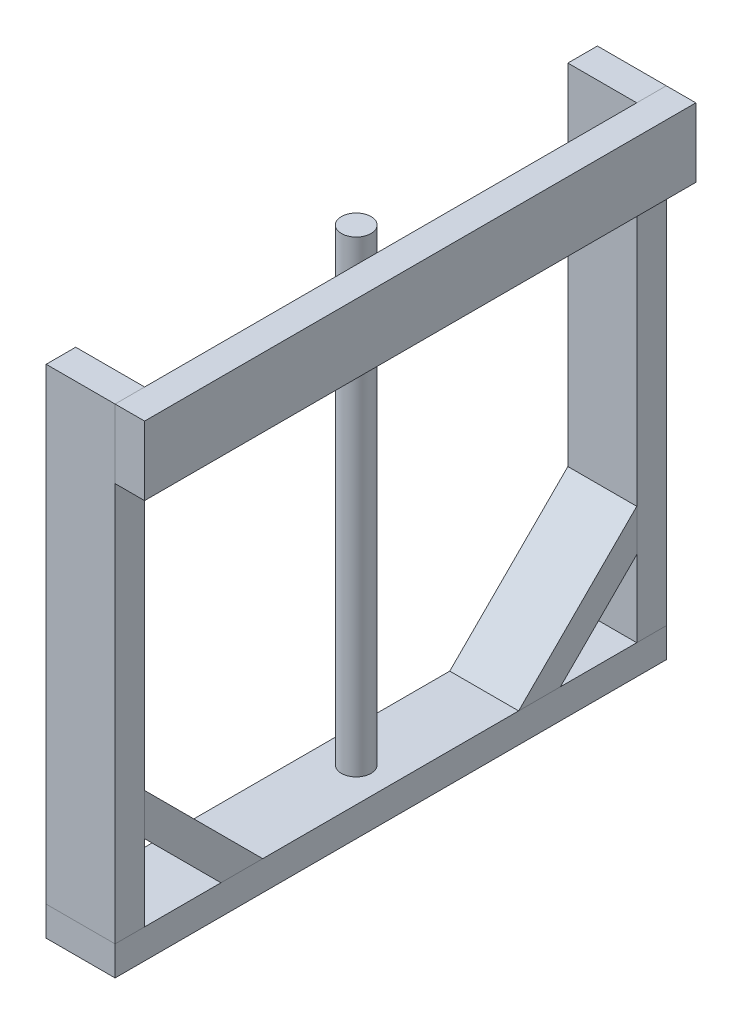
SolidWorks part; units mm, degrees
ref_plane "Front Plane" through (0, 0, 0) normal (0, 0, 1) x (1, 0, 0)
ref_plane "Top Plane" through (0, 0, 0) normal (0, 1, 0) x (1, 0, 0)
ref_plane "Right Plane" through (0, 0, 0) normal (1, 0, 0) x (0, 0, -1)
sketch "Sketch1" plane through (0, 0, 0) normal (1, 0, 0) x (0, 0, -1)
  line L1 (-355.6, 0) -> (355.6, 0)
  line L2 (-355.6, 0) -> (-355.6, -88.9)
  line L3 (-355.6, -88.9) -> (355.6, -88.9)
  line L4 (355.6, 0) -> (355.6, -88.9)
  dimension "D1" = 711.2
  dimension "D2" = 88.9
extrude "Top_Cross_Support" add sketch "Sketch1" along normal blind 38.1
sketch "Sketch2" plane through (0, 0, 0) normal (-1, 0, 0) x (0, 0, 1)
  line L1 (355.6, 0) -> (317.5, 0)
  line L2 (355.6, 0) -> (355.6, -603.25)
  line L3 (355.6, -603.25) -> (317.5, -603.25)
  line L4 (317.5, 0) -> (317.5, -603.25)
  dimension "D1" = 603.25
  dimension "D2" = 38.1
extrude "Leg" add sketch "Sketch2" along normal blind 88.9 separate body
mirror "Leg_Mirror" about plane through (0, 0, 0) normal (0, 0, 1) of bodies 102
sketch "Sketch4" plane through (0, -603.25, 0) normal (0, -1, 0) x (1, 0, 0)
  line L1 (0, 355.6) -> (-88.9, 355.6)
  line L2 (0, 355.6) -> (0, -355.6)
  line L3 (0, -355.6) -> (-88.9, -355.6)
  line L4 (-88.9, 355.6) -> (-88.9, -355.6)
extrude "Bottom_Cross_Support" add sketch "Sketch4" along normal blind 38.1 separate body
sketch "Sketch5" plane through (0, 0, 0) normal (1, 0, 0) x (0, 0, -1)
  line L0 (-218.9815, -603.25) -> (-317.5, -504.7315)
  line L1 (355.6, -603.25) -> (-355.6, -603.25) construction
  line L2 (-317.5, 0) -> (-317.5, -603.25) construction
  line L3 (-317.5, -450.85) -> (-165.1, -603.25)
  line L4 (-165.1, -603.25) -> (-218.9815, -603.25)
  line L5 (-317.5, -504.7315) -> (-317.5, -450.85)
  dimension "D1" = 38.1
  dimension "D2" = 152.4
extrude "Low_Diagonal_Support" add sketch "Sketch5" against normal blind 88.9 separate body
mirror "Low_Diagonal_Support_Mirror" about plane through (0, 0, 0) normal (0, 0, 1) of bodies 106
sketch "Sketch6" plane through (0, -603.25, 0) normal (0, 1, 0) x (1, 0, 0)
  line L0 (-88.9, -355.6) -> (-88.9, 355.6) construction
  line L1 (0, 355.6) -> (0, -355.6) construction
  line L2 (0, 0) -> (-88.9, 0) construction
  circle A0 centre (-44.45, 0) radius 19.05
  dimension "D1" = 38.1
extrude "Actuator" add sketch "Sketch6" along normal blind 603.25 separate body
equation "\"height\"=23.75"
equation "\"D1@Sketch2\"=\"height\""
equation "\"D1@Actuator\"=\"height\""
